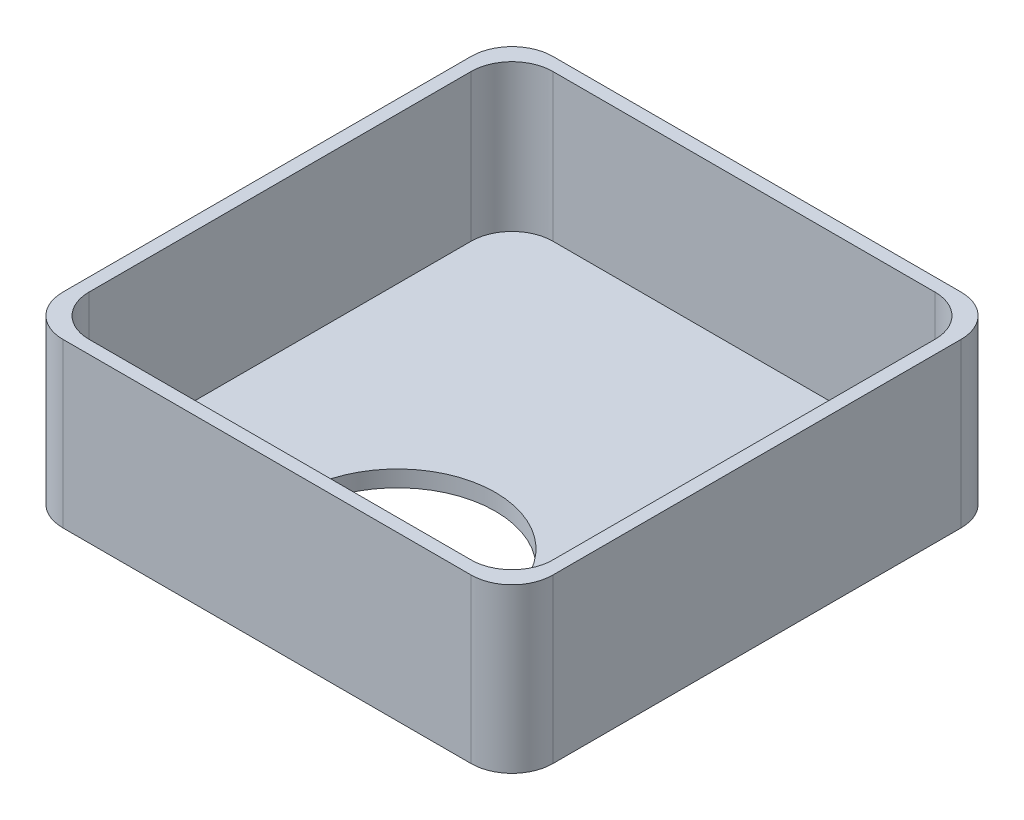
SolidWorks part; units mm, degrees
ref_plane "Спереди" through (0, 0, 0) normal (0, 0, 1) x (1, 0, 0)
ref_plane "Сверху" through (0, 0, 0) normal (0, 1, 0) x (1, 0, 0)
ref_plane "Справа" through (0, 0, 0) normal (1, 0, 0) x (0, 0, -1)
sketch "Sketch1" plane through (0, 0, 0) normal (0, 1, 0) x (1, 0, 0)
  line L1 (-30, -30) -> (30, -30)
  line L2 (-30, -30) -> (-30, 30)
  line L3 (-30, 30) -> (30, 30)
  line L4 (30, -30) -> (30, 30)
  line L5 (-30, -30) -> (30, 30) construction
  line L6 (-30, 30) -> (30, -30) construction
  point P0 (0, 0)
  dimension "D1" = 60
  dimension "D2" = 60
extrude "Boss-Extrude1" add sketch "Sketch1" along normal blind 20
sketch "Sketch2" plane through (0, 20, 0) normal (0, 1, 0) x (1, 0, 0)
  line L8 (28.4, -28.4) -> (28.4, 28.4)
  line L9 (28.4, 28.4) -> (-28.4, 28.4)
  line L10 (-28.4, 28.4) -> (-28.4, -28.4)
  line L11 (-28.4, -28.4) -> (28.4, -28.4)
  line L12 (28.4, -28.4) -> (28.4, 28.4)
  line L13 (28.4, 28.4) -> (-28.4, 28.4)
  line L14 (-28.4, 28.4) -> (-28.4, -28.4)
  line L15 (-28.4, -28.4) -> (28.4, -28.4)
  dimension "D1" = 1.6
extrude "Cut-Extrude1" cut sketch "Sketch2" against normal offset from surface (18 mm away) 2 up to face at (0, 0, 0)
fillet "Fillet1" radius 5 8 edges at (30, 10, 30) (-30, 10, 30) (-30, 10, -30) (30, 10, -30) (-28.4, 11, 28.4) (28.4, 11, 28.4) (28.4, 11, -28.4) (-28.4, 11, -28.4)
sketch "Sketch3" plane through (0, 0, 0) normal (0, -1, 0) x (1, 0, 0)
  circle A0 centre (-0.2778, 13.7491) radius 12
  dimension "D1" = 24
extrude "Cut-Extrude2" cut sketch "Sketch3" against normal up to next
